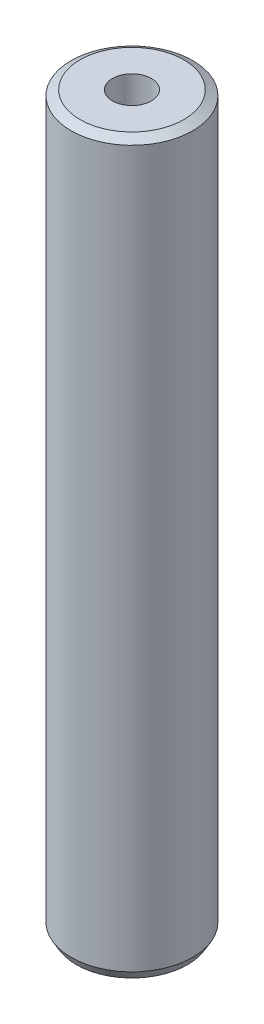
SolidWorks part; units mm, degrees
ref_plane "Front Plane" through (0, 0, 0) normal (0, 0, 1) x (1, 0, 0)
ref_plane "Top Plane" through (0, 0, 0) normal (0, 1, 0) x (1, 0, 0)
ref_plane "Right Plane" through (0, 0, 0) normal (1, 0, 0) x (0, 0, -1)
sketch "Sketch1" plane through (0, 0, 0) normal (0, 1, 0) x (1, 0, 0)
  circle A0 centre (0, 0) radius 50
  dimension "SHAFT_OD" = 100
extrude "Boss-Extrude1" add sketch "Sketch1" along normal blind 600
sketch "Sketch2" plane through (0, 0, 0) normal (0, 1, 0) x (1, 0, 0)
  circle A0 centre (0, 0) radius 16.0107
  dimension "BORE_D" = 32.0213
extrude "Cut-Extrude1" cut sketch "Sketch2" along normal through all
chamfer "Chamfer1" distance 4.2578 angle 60 2 edges at (0, 600, 50) (0, 0, 50) first distance on face at (0, 600, 50) first distance on face at (0, 0, 16.0107)
